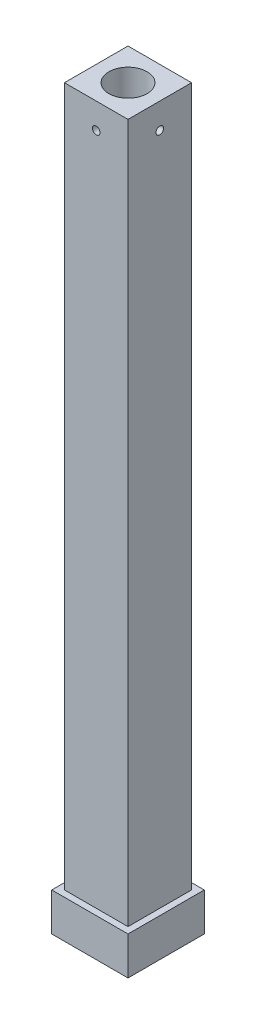
SolidWorks part; units mm, degrees
ref_plane "前视基准面" through (0, 0, 0) normal (0, 0, 1) x (1, 0, 0)
ref_plane "上视基准面" through (0, 0, 0) normal (0, 1, 0) x (1, 0, 0)
ref_plane "右视基准面" through (0, 0, 0) normal (1, 0, 0) x (0, 0, -1)
other "Configuration Table"
sketch "草图1" plane through (0, 0, 0) normal (0, 1, 0) x (1, 0, 0)
  line L1 (2.8868, 0) -> (1.4434, 2.5)
  line L2 (1.4434, 2.5) -> (-1.4434, 2.5)
  line L3 (-1.4434, 2.5) -> (-2.8868, 0)
  line L4 (-2.8868, 0) -> (-1.4434, -2.5)
  line L5 (-1.4434, -2.5) -> (1.4434, -2.5)
  line L6 (1.4434, -2.5) -> (2.8868, 0)
  line L7 (-2.5, -2.5) -> (2.5, -2.5)
  line L8 (-2.5, -2.5) -> (-2.5, 2.5)
  line L9 (-2.5, 2.5) -> (2.5, 2.5)
  line L10 (2.5, -2.5) -> (2.5, 2.5)
  line L11 (-2.5, -2.5) -> (2.5, 2.5) construction
  line L12 (-2.5, 2.5) -> (2.5, -2.5) construction
  line L13 (-3, -3) -> (3, -3)
  line L14 (-3, -3) -> (-3, 3)
  line L15 (-3, 3) -> (3, 3)
  line L16 (3, -3) -> (3, 3)
  line L17 (-3, -3) -> (3, 3) construction
  line L18 (-3, 3) -> (3, -3) construction
  circle A0 centre (0, 0) radius 2.5 construction
  circle A1 centre (0, 0) radius 1.5
  dimension "D1" = 5
  dimension "D3" = 3
  dimension "D2" = 5
  dimension "D4" = 6
extrude "凸台-拉伸1" add sketch "草图1" along normal blind 58 contours L9 L10 L7 L8
extrude "凸台-拉伸2" add sketch "草图1<5>" along normal blind 3 contours L15 L16 L13 L14
sketch "草图1<5>" plane through (0, 0, 0) normal (0, 1, 0) x (1, 0, 0) same geometry as "草图1"
extrude "切除-拉伸1" cut sketch "草图1<3>" along normal through all contours A1 region at (0, 0, 0)
sketch "草图1<3>" plane through (0, 0, 0) normal (0, 1, 0) x (1, 0, 0) same geometry as "草图1"
extrude "切除-拉伸2" cut sketch "草图1<4>" along normal blind 2 contours L1 L2 L3 L4 L5 L6
sketch "草图1<4>" plane through (0, 0, 0) normal (0, 1, 0) x (1, 0, 0) same geometry as "草图1"
sketch "草图3" plane through (0, 0, 2.5) normal (0, 0, 1) x (1, 0, 0)
  line L0 (-2.5, 58) -> (2.5, 58) construction
  line L1 (-2.5, 56) -> (2.5, 56) construction
  line L2 (-2.5, 58) -> (-2.5, 3) construction
  line L3 (2.5, 58) -> (2.5, 3) construction
  circle A0 centre (0, 56) radius 0.3
  dimension "D1" = 0.6
  dimension "D2" = 2
extrude "切除-拉伸3" cut sketch "草图3" against normal through all
sketch "草图4" plane through (-2.5, 0, 0) normal (-1, 0, 0) x (0, 0, 1)
  line L0 (-2.5, 56) -> (2.5, 56) construction
  line L1 (-2.5, 58) -> (-2.5, 3) construction
  line L2 (2.5, 58) -> (2.5, 3) construction
  line L3 (2.5, 58) -> (-2.5, 58) construction
  circle A0 centre (0, 56) radius 0.3
  dimension "D1" = 0.6
  dimension "D2" = 2
extrude "切除-拉伸4" cut sketch "草图4" against normal through all
